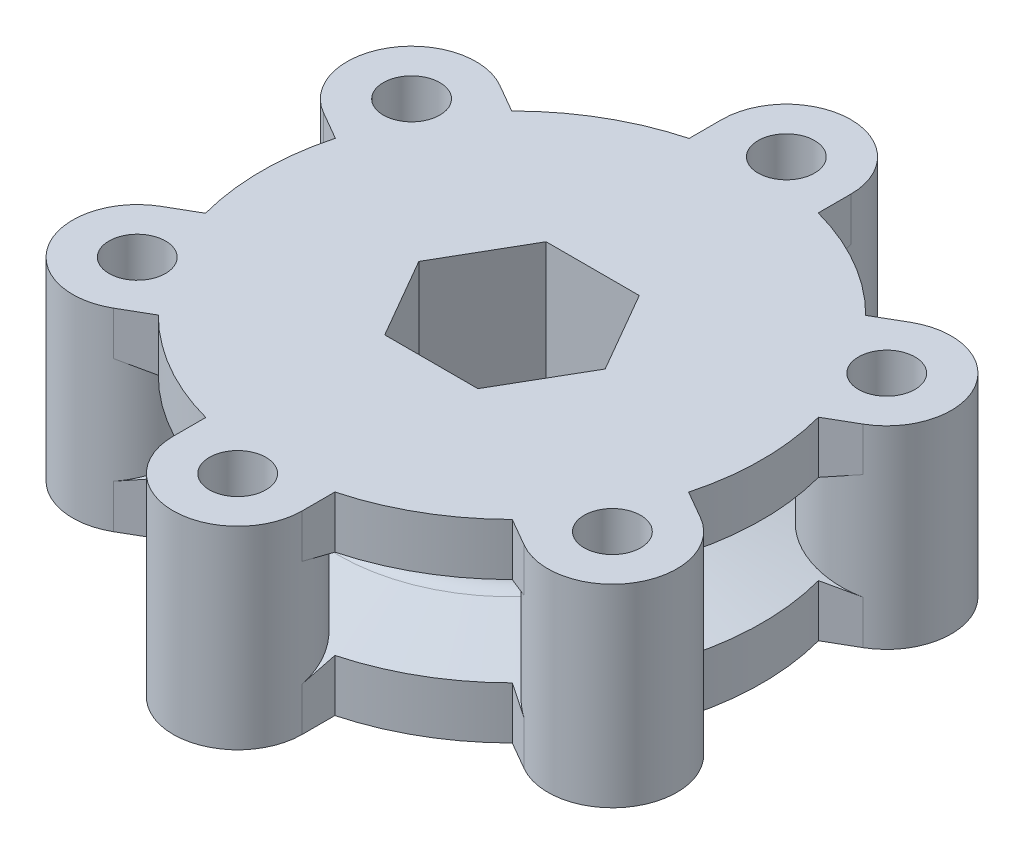
SolidWorks part; units mm, degrees
material "PLA/ABS"
ref_plane "Front Plane" through (0, 0, 0) normal (0, 0, 1) x (1, 0, 0)
ref_plane "Top Plane" through (0, 0, 0) normal (0, 1, 0) x (1, 0, 0)
ref_plane "Right Plane" through (0, 0, 0) normal (1, 0, 0) x (0, 0, -1)
other "Bounding Box"
ref_plane "Default Plane" through (13.8565, 3.175, 6.7999) normal (0, -1, 0) x (-1, 0, 0)
sketch "Sketch1" plane through (0, 0, 0) normal (0, 1, 0) x (1, 0, 0)
  line L0 (22.4506, -22.4506) -> (0, 0) construction
  line L1 (0, 0) -> (22.4506, 22.4506) construction
  line L2 (0, 0) -> (0, 31.75) construction
  circle A0 centre (0, 0) radius 31.75
  point P3 (0, 31.75)
  point P4 (31.75, 0)
  point P5 (-31.75, 0)
  point P6 (0, -31.75)
  point P7 (22.4506, 22.4506)
  point P8 (22.4506, -22.4506)
  dimension "D1" = 63.5
  dimension "D2" = 45
extrude "Boss-Extrude1" add sketch "Sketch1" along normal mid plane 15.24
ref_plane "Plane2" through (-31.75, 0, 0) normal (-1, 0, 0) x (0, 0, 1)
sketch "Sketch9" plane through (-31.75, 0, 0) normal (-1, 0, 0) x (0, 0, 1)
  line L0 (-0.635, -7.62) -> (0.635, -7.62)
  line L1 (-31.75, -7.62) -> (31.75, -7.62) construction
  line L2 (0.635, -7.62) -> (0.635, 0)
  line L3 (31.75, 7.62) -> (-31.75, 7.62) construction
  line L5 (-0.635, 0) -> (-0.635, -7.62)
  line L6 (0.635, -7.62) -> (0, -7.62) construction
  line L7 (0, -7.62) -> (0, 7.62) construction
  line L9 (-0.635, 0) -> (0.635, 0) construction
  line L10 (0.635, 0) -> (0.635, 7.62)
  line L11 (0.635, 7.62) -> (-0.635, 7.62)
  line L13 (-0.635, 7.62) -> (-0.635, 0)
  point P14 (0, 0)
  dimension "D2" = 1.27
extrude "Cut-Extrude4" cut sketch "Sketch9" against normal blind 0.635
sketch "Sketch4" plane through (0, 0, 0) normal (0, 0, 1) x (1, 0, 0)
  line L0 (-31.75, -7.62) -> (-29.21, -7.62)
  line L1 (-31.7436, -7.62) -> (31.75, -7.62) construction
  line L4 (31.75, 7.62) -> (-31.7436, 7.62) construction
  line L5 (-29.21, 7.62) -> (-31.75, 7.62)
  line L6 (-31.75, 7.62) -> (-31.75, -7.62)
  line L7 (-6.35, 0) -> (0, 0) construction
  line L8 (-29.21, -7.62) -> (-29.21, -6.0325)
  line L9 (-29.21, -6.0325) -> (-6.35, 0)
  line L10 (-6.35, 0) -> (-29.21, 6.0325)
  line L11 (-29.21, 6.0325) -> (-29.21, 7.62)
  point P17 (-31.75, 0)
  dimension "D1" = 2.54
  dimension "D2" = 25.4
  dimension "D3" = 1.5875
pattern_circular "CirPattern2" count 20 over 360 about axis through (0, -7.62, 0) along (0, 1, 0) of "Cut-Extrude4"
ref_axis "Axis1" through (0, -9.0805, 0) along (0, 1, 0)
sketch "Sketch3" plane through (0, 7.62, 0) normal (0, 1, 0) x (1, 0, 0)
  line L0 (0, 0) -> (0, 21.59) construction
  line L1 (0, 21.59) -> (0, 31.75) construction
  circle A0 centre (0, 21.59) radius 2.2225
  circle A1 centre (0, 0) radius 31.75 construction
  circle A2 centre (0, 21.59) radius 5.08
  dimension "D2" = 4.445
  dimension "D3" = 10.16
  dimension "D1" = 10.16
move or copy body "Body-Move/Copy1" [suppressed] parameters "D1"=0, "D2"=0, "D3"=0
revolve "Cut-Revolve2" cut sketch "Sketch4" angle 360 about axis through (0, -9.0805, 0) along (0, 1, 0)
sketch "Sketch5" plane through (0, 7.62, 0) normal (0, 1, 0) x (1, 0, 0)
  circle A0 centre (0, 21.59) radius 5.08
  circle A1 centre (0, 21.59) radius 2.2225 construction
  circle A3 centre (0, 21.59) radius 2.2225
  circle A4 centre (0, 21.59) radius 5.08 construction
extrude "Boss-Extrude2" add sketch "Sketch5" against normal through all
sketch "Sketch12" plane through (0, 7.62, 0) normal (0, 1, 0) x (1, 0, 0)
  line L0 (-18.6975, 10.795) -> (0, 0) construction
  line L1 (-18.6975, -10.795) -> (-18.6975, 10.795) construction
  line L2 (-18.6975, 10.795) -> (0, 21.59) construction
  line L3 (-18.6975, -10.795) -> (0, 0) construction
  line L4 (0, 0) -> (0, 21.59) construction
  circle A0 centre (-18.6975, 10.795) radius 5.08
  circle A1 centre (0, 21.59) radius 5.08 construction
  dimension "D3" = 120
extrude "Boss-Extrude6" add sketch "Sketch12" against normal through all
sketch "Sketch17" plane through (0, 0, 0) normal (0, 1, 0) x (1, 0, 0)
  line L0 (0, 21.59) -> (0, 0) construction
  line L1 (0, 0) -> (-18.6975, 10.795) construction
  line L2 (0, 0) -> (-18.6975, -10.795) construction
  line L3 (-23.0969, -13.335) -> (-25.2966, -14.605)
  line L4 (0, 26.67) -> (0, 29.21)
  line L5 (-21.2375, -6.3956) -> (-19.0103, -5.1097)
  line L6 (-19.0103, 5.1097) -> (-21.2375, 6.3956)
  line L7 (-16.1575, 15.1944) -> (-13.9303, 13.9085)
  line L8 (-5.08, 21.59) -> (-5.08, 19.0182)
  circle A0 centre (0, 21.59) radius 5.08 construction
  circle A1 centre (-18.6975, 10.795) radius 5.08 construction
  arc A2 (0, 26.67) -> (-5.08, 21.59) centre (0, 21.59) ccw
  arc A3 (-16.1575, 15.1944) -> (-21.2375, 6.3956) centre (-18.6975, 10.795) ccw
  arc A5 (-5.08, 19.0182) -> (-13.9303, 13.9085) centre (0, 0) ccw
  circle A6 centre (0, 21.59) radius 2.2225 construction
  arc A7 (-21.2375, -6.3956) -> (-23.0969, -13.335) centre (-18.6975, -10.795) ccw
  circle A8 centre (0, 0) radius 29.21 construction
  circle A9 centre (0, 21.59) radius 2.2225
  circle A10 centre (0, 0) radius 29.21 construction
  arc A11 (0, 29.21) -> (-25.2966, -14.605) centre (0, 0) ccw
  arc A12 (-19.0103, 5.1097) -> (-19.0103, -5.1097) centre (0, 0) ccw
  circle A13 centre (-18.6975, 10.795) radius 2.2225
  circle A15 centre (-18.6975, -10.795) radius 2.2225
  dimension "D1" = 9.525
extrude "Cut-Extrude5" cut sketch "Sketch17" against normal through all both and the other way through all
pattern_circular "CirPattern1" count 3 over 360 about axis through (0, 6.0325, 0) along (0, -1, 0) of "Boss-Extrude2", "Boss-Extrude6", "Cut-Extrude5"
sketch "Sketch18" plane through (0, -7.62, 0) normal (0, -1, 0) x (1, 0, 0)
  circle A0 centre (0, 0) radius 19.685 construction
  circle A1 centre (0, 0) radius 12.7
  arc A2 (-5.08, 19.0182) -> (-13.9303, 13.9085) centre (0, 0) ccw construction
  circle A3 centre (0, 0) radius 6.35 construction
  circle A4 centre (0, 0) radius 6.35 construction
  circle A5 centre (0, 0) radius 31.75 construction
  dimension "D1" = 19.05
extrude "Boss-Extrude9" add sketch "Sketch18" against normal through all
fillet "Fillet5" radius 1.27 2 edges at (0, -1.6757, -12.7) (0, 1.6757, 12.7)
sketch "Sketch24" plane through (0, -7.62, 0) normal (0, -1, 0) x (1, 0, 0)
  line L1 (3.6662, -6.35) -> (7.3323, 0)
  line L2 (7.3323, 0) -> (3.6662, 6.35)
  line L3 (3.6662, 6.35) -> (-3.6662, 6.35)
  line L4 (-3.6662, 6.35) -> (-7.3323, 0)
  line L5 (-7.3323, 0) -> (-3.6662, -6.35)
  line L6 (-3.6662, -6.35) -> (3.6662, -6.35)
  circle A0 centre (0, 0) radius 4 construction
  circle A1 centre (0, 0) radius 6.35 construction
  dimension "D1" = 8
  dimension "D2" = 12.7
extrude "Cut-Extrude7" cut sketch "Sketch24" against normal through all
combine bodies "Combine3" [suppressed] bodies to combine 116 167
delete or keep bodies "Body-Delete/Keep 4" [suppressed] type keep bodies bodies 117
sketch "Sketch7" [suppressed] plane through (0, -8.255, 0) normal (0, -1, 0) x (1, 0, 0)
  circle A0 centre (0, 0) radius 44.45
  circle A1 centre (0, 0) radius 38.1 construction
  dimension "D1" = 6.35
extrude "Boss-Extrude4" [suppressed] add sketch "Sketch7" against normal offset from surface (19.685 mm away) 3.175 separate body up to face at (0, 7.62, 0) offset beyond the face yes
combine bodies "Combine2" [suppressed] operation type add bodies to combine 110 114
sketch "Sketch15" [suppressed] plane through (0, 0, 0) normal (1, 0, 0) x (0, 0, -1)
  line L0 (-38.1, -8.255) -> (-43.18, -13.335)
  line L1 (-43.18, -13.335) -> (-36.83, -13.335)
  line L2 (-36.83, -13.335) -> (-31.75, -8.255)
  line L3 (-31.75, -8.255) -> (-38.1, -8.255)
  dimension "D1" = 5.08
  dimension "D2" = 45
  dimension "D3" = 6.35
ref_axis "Axis2" [suppressed] through (0, -9.0805, 0) along (0, 1, 0)
revolve "Revolve1" [suppressed] add sketch "Sketch15" angle 360 about axis through (0, -9.0805, 0) along (0, 1, 0)
fillet "Fillet4" [suppressed] radius 6.35
sketch "Sketch27" [suppressed] plane through (0, 11.43, 0) normal (0, 1, 0) x (1, 0, 0)
  line L0 (37.5671, 6.35) -> (44.45, 6.35)
  line L1 (44.45, -6.35) -> (37.5671, -6.35)
  line L2 (38.1, 0) -> (44.45, 0) construction
  circle A0 centre (44.45, 0) radius 1.905
  arc A1 (37.5671, -6.35) -> (37.5671, 6.35) centre (0, 0) ccw
  circle A2 centre (0, 0) radius 38.1 construction
  arc A3 (44.45, 6.35) -> (44.45, -6.35) centre (44.45, 0) cw
  dimension "D2" = 3.81
  dimension "D3" = 6.35
  dimension "D1" = 6.35
extrude "Boss-Extrude13" [suppressed] add sketch "Sketch27" against normal blind 9.525
pattern_circular "CirPattern7" [suppressed] count 3 over 360 of bodies 177
split "Split1" [suppressed] bodies to split 124
sketch "Sketch19" [suppressed] plane through (0, 11.43, 0) normal (0, 1, 0) x (1, 0, 0)
  line L0 (-20.447, 35.4152) -> (-19.177, 33.2155)
  line L1 (-20.447, -35.4152) -> (-19.177, -33.2155)
  line L2 (-40.894, 0) -> (0, 0) construction
  arc A0 (-19.177, 33.2155) -> (-19.177, -33.2155) centre (0, 0) ccw
  circle A1 centre (0, 0) radius 38.1 construction
  arc A2 (-20.447, 35.4152) -> (-20.447, -35.4152) centre (0, 0) ccw
  dimension "D2" = 2.54
  dimension "D3" = 0.254
  dimension "D1" = 120
extrude "Boss-Extrude10" [suppressed] add sketch "Sketch19" against normal blind 6.35 separate body
sketch "Sketch21" [suppressed] plane through (0, 11.43, 0) normal (0, 1, 0) x (1, 0, 0)
  line L0 (-19.177, 33.2155) -> (-19.05, 32.9956)
  line L1 (-19.177, -33.2155) -> (-19.05, -32.9956)
  line L2 (-19.177, 33.2155) -> (-20.447, 35.4152) construction
  line L3 (-20.447, -35.4152) -> (-19.177, -33.2155) construction
  arc A1 (-19.177, 33.2155) -> (-19.177, -33.2155) centre (0, 0) ccw construction
  arc A2 (-19.05, 32.9956) -> (-19.05, -32.9956) centre (0, 0) ccw
  arc A3 (-19.177, 33.2155) -> (-19.177, -33.2155) centre (0, 0) ccw
  circle A4 centre (0, 0) radius 38.1 construction
extrude "Boss-Extrude11" [suppressed] add sketch "Sketch21" against normal blind 3.1496
pattern_circular "CirPattern6" [suppressed] count 3 over 360 reverse direction yes of bodies 137 132
combine bodies "Combine4" [suppressed] bodies to combine 137 137 135 134
chamfer "Chamfer4" [suppressed] distance 0.635 angle 45
delete or keep bodies "Body-Delete/Keep 1" [suppressed] type delete bodies bodies 133
delete or keep bodies "Body-Delete/Keep 2" [suppressed] type delete bodies bodies 121
mirror "Mirror1" [suppressed] about plane through (0, 0, 0) normal (1, 0, 0) of bodies 121
delete or keep bodies "Body-Delete/Keep 3" [suppressed] type delete bodies bodies 121
sketch "Sketch28" [suppressed] plane through (0, 8.255, 0) normal (0, -1, 0) x (1, 0, 0)
  circle A0 centre (0, 0) radius 15.24
  dimension "D1" = 30.48
extrude "Boss-Extrude14" [suppressed] add sketch "Sketch28" along normal blind 0.635
sketch "Sketch29" [suppressed] plane through (0, 7.62, 0) normal (0, -1, 0) x (1, 0, 0)
  circle A0 centre (0, 0) radius 9.144
  dimension "D1" = 18.288
extrude "Boss-Extrude15" [suppressed] add sketch "Sketch29" along normal blind 10.16
sketch "Sketch30" [suppressed] plane through (0, -8.255, 0) normal (0, -1, 0) x (1, 0, 0)
  circle A12 centre (0, 0) radius 30.48
  circle A13 centre (0, 0) radius 27.94
  circle A14 centre (0, 0) radius 31.75 construction
  dimension "D1" = 1.27
  dimension "D2" = 2.54
extrude "Boss-Extrude16" [suppressed] add sketch "Sketch30" along normal blind 1.6002 separate body
sketch "Sketch31" [suppressed] plane through (0, -9.8552, 0) normal (0, -1, 0) x (1, 0, 0)
  line L0 (-5.9055, 21.59) -> (-5.9055, 29.9024)
  line L1 (-5.9055, 29.9024) -> (5.9055, 29.9024)
  line L2 (5.9055, 29.9024) -> (5.9055, 21.59)
  line L3 (0, 0) -> (0, 21.59) construction
  line L5 (-1.5875, 15.9019) -> (1.5875, 15.9019) construction
  line L6 (-1.5875, 15.9019) -> (-1.5875, 7.62)
  line L7 (-1.5875, 7.62) -> (1.5875, 7.62)
  line L8 (1.5875, 15.9019) -> (1.5875, 7.62)
  line L9 (-1.5875, 15.9019) -> (1.5875, 7.62) construction
  line L10 (-1.5875, 7.62) -> (1.5875, 15.9019) construction
  arc A0 (-1.5875, 15.9019) -> (-5.9055, 21.59) centre (0, 21.59) cw
  circle A1 centre (0, 21.59) radius 2.7305
  arc A2 (5.9055, 21.59) -> (1.5875, 15.9019) centre (0, 21.59) cw
  circle A3 centre (0, 21.59) radius 2.2225 construction
  circle A4 centre (0, 0) radius 30.48 construction
  point P6 (0, 11.7609)
  dimension "D1" = 3.175
  dimension "D2" = 5.461
  dimension "D3" = 7.62
  dimension "D4" = 3.175
extrude "Boss-Extrude17" [suppressed] add sketch "Sketch31" against normal up to surface (1.6002 mm away) up to face at (0, -7.62, 0)
fillet "Fillet6" [suppressed] radius 2.54
pattern_circular "CirPattern8" [suppressed] count 6 over 360 of bodies 182
sketch "Sketch32" [suppressed] plane through (0, -9.8552, 0) normal (0, -1, 0) x (1, 0, 0)
  line L0 (0, 0) -> (-2.3034, 32.9396) construction
  line L1 (2.3034, 32.9396) -> (0.3104, 30.4784)
  line L2 (0, 0) -> (0, 33.02) construction
  line L3 (-1.8597, 30.4232) -> (-2.3034, 32.9396)
  line L4 (-2.3034, 32.9396) -> (-0.3104, 30.4784)
  line L5 (-0.3104, 30.4784) -> (-1.8597, 30.4232)
  line L6 (1.8597, 30.4232) -> (2.3034, 32.9396)
  line L7 (0.3104, 30.4784) -> (1.8597, 30.4232)
  circle A0 centre (0, 0) radius 30.48 construction
  circle A1 centre (0, 0) radius 33.02 construction
  circle A2 centre (0, 0) radius 31.75 construction
  dimension "D2" = 1.27
  dimension "D1" = 6
  dimension "D3" = 35
  dimension "D4" = 4
extrude "Boss-Extrude18" [suppressed] add sketch "Sketch32" against normal up to surface (1.6002 mm away) up to face at (0, -7.62, 0)
fillet "Fillet7" [suppressed] radius 0.635
pattern_circular "CirPattern9" [suppressed] count 10 over 360 of bodies 184
delete or keep bodies "Body-Delete/Keep 5" [suppressed] bodies 185
sketch "Sketch33" [suppressed] plane through (0, -9.8552, 0) normal (0, -1, 0) x (1, 0, 0)
  line L1 (3.7028, -6.4135) -> (7.4057, 0)
  line L2 (7.4057, 0) -> (3.7028, 6.4135)
  line L3 (3.7028, 6.4135) -> (-3.7028, 6.4135)
  line L4 (-3.7028, 6.4135) -> (-7.4057, 0)
  line L5 (-7.4057, 0) -> (-3.7028, -6.4135)
  line L6 (-3.7028, -6.4135) -> (3.7028, -6.4135)
  circle A0 centre (0, 0) radius 6.4135 construction
  circle A1 centre (0, 0) radius 9.525
  dimension "D2" = 19.05
  dimension "D1" = 12.827
extrude "Boss-Extrude19" [suppressed] add sketch "Sketch33" against normal up to surface (1.6002 mm away) up to face at (0, -7.62, 0)
